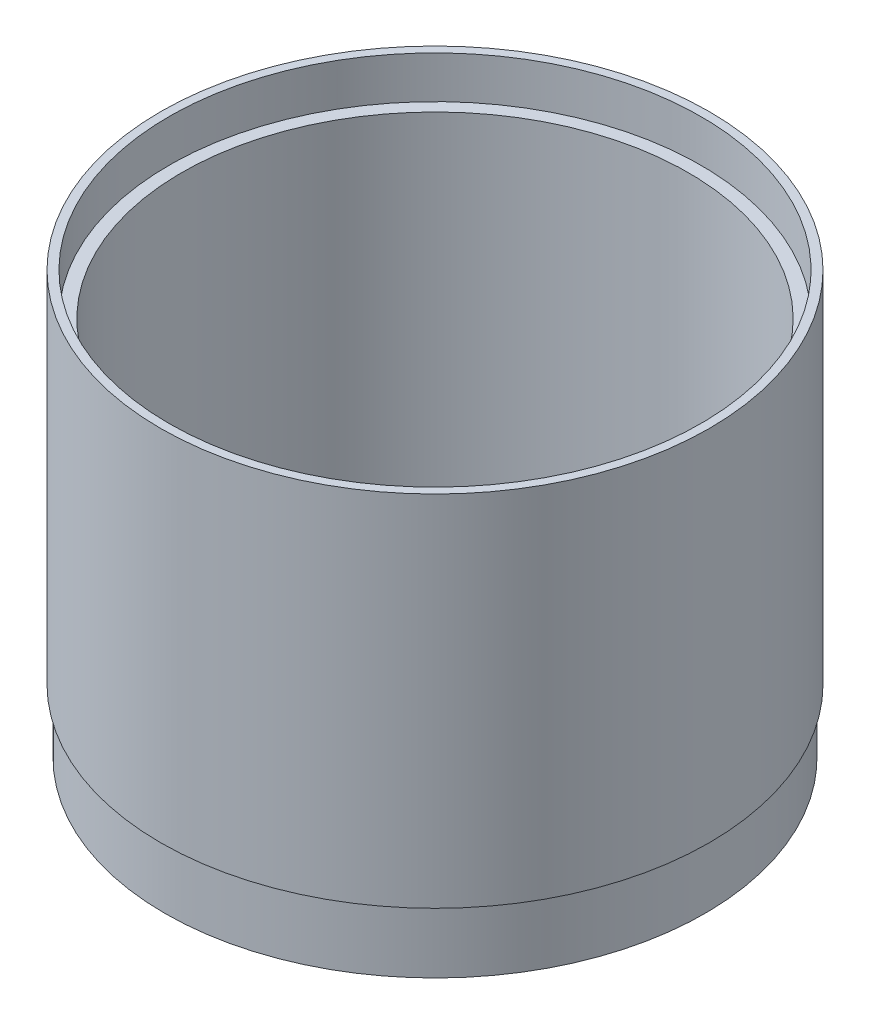
SolidWorks part; units mm, degrees
material "HYPALON"
ref_plane "Front Plane" through (0, 0, 0) normal (0, 0, 1) x (1, 0, 0)
ref_plane "Top Plane" through (0, 0, 0) normal (0, 1, 0) x (1, 0, 0)
ref_plane "Right Plane" through (0, 0, 0) normal (1, 0, 0) x (0, 0, -1)
sketch "Szkic1" plane through (0, 0, 0) normal (0, 0, 1) x (1, 0, 0)
  line L0 (-64, 0) -> (0, 0)
  line L1 (-64, 0) -> (-60, 0)
  line L2 (-64, 0) -> (-64, 15)
  line L3 (-64, 15) -> (-65, 15)
  line L4 (-65, 15) -> (-65, 28.5618)
  line L5 (-60, 0) -> (-60, 90)
  line L6 (-60, 90) -> (-63, 90)
  line L7 (-63, 90) -> (-63, 100)
  line L8 (-63, 100) -> (-65, 100)
  line L9 (-65, 100) -> (-65, 28.5618)
  line L10 (0, 35.541) -> (0, 0)
  dimension "D1" = 65
  dimension "D2" = 15
  dimension "D3" = 1
  dimension "D4" = 10
  dimension "D5" = 2
  dimension "D6" = 5
  dimension "D7" = 60
  dimension "D8" = 90
revolve "Obrót1" add sketch "Szkic1" angle 360 about L10 region at (-62.5, 48.4341, 0)
